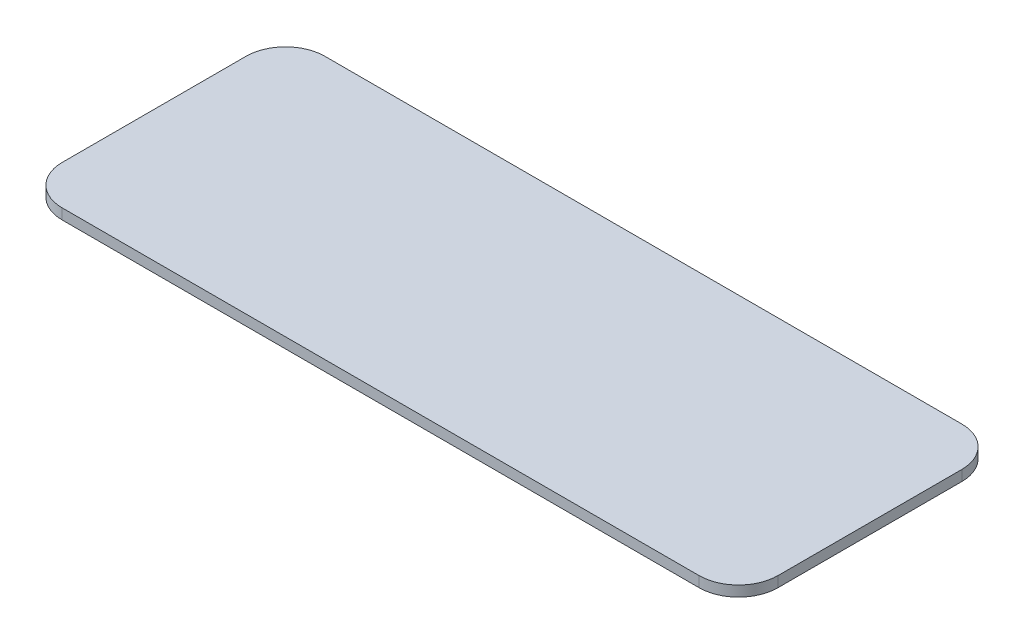
SolidWorks part; units mm, degrees
ref_plane "Ebene vorne" through (0, 0, 0) normal (0, 0, 1) x (1, 0, 0)
ref_plane "Ebene oben" through (0, 0, 0) normal (0, 1, 0) x (1, 0, 0)
ref_plane "Ebene rechts" through (0, 0, 0) normal (1, 0, 0) x (0, 0, -1)
sketch "Skizze1" plane through (0, 0, 0) normal (0, 1, 0) x (1, 0, 0)
  line L1 (-48.5, 20) -> (48.5, 20)
  line L2 (-54.5, 14) -> (-54.5, -14)
  line L3 (-48.5, -20) -> (48.5, -20)
  line L4 (54.5, 14) -> (54.5, -14)
  line L5 (-54.5, 20) -> (54.5, -20) construction
  line L6 (-54.5, -20) -> (54.5, 20) construction
  arc A0 (48.5, 20) -> (54.5, 14) centre (48.5, 14) cw
  arc A1 (48.5, -20) -> (54.5, -14) centre (48.5, -14) ccw
  arc A2 (-54.5, -14) -> (-48.5, -20) centre (-48.5, -14) ccw
  arc A3 (-48.5, 20) -> (-54.5, 14) centre (-48.5, 14) ccw
  point P0 (0, 0)
  dimension "D3" = 6
  dimension "D1" = 40
  dimension "D2" = 109
extrude "Aufsatz-Linear austragen1" add sketch "Skizze1" along normal blind 1.6
